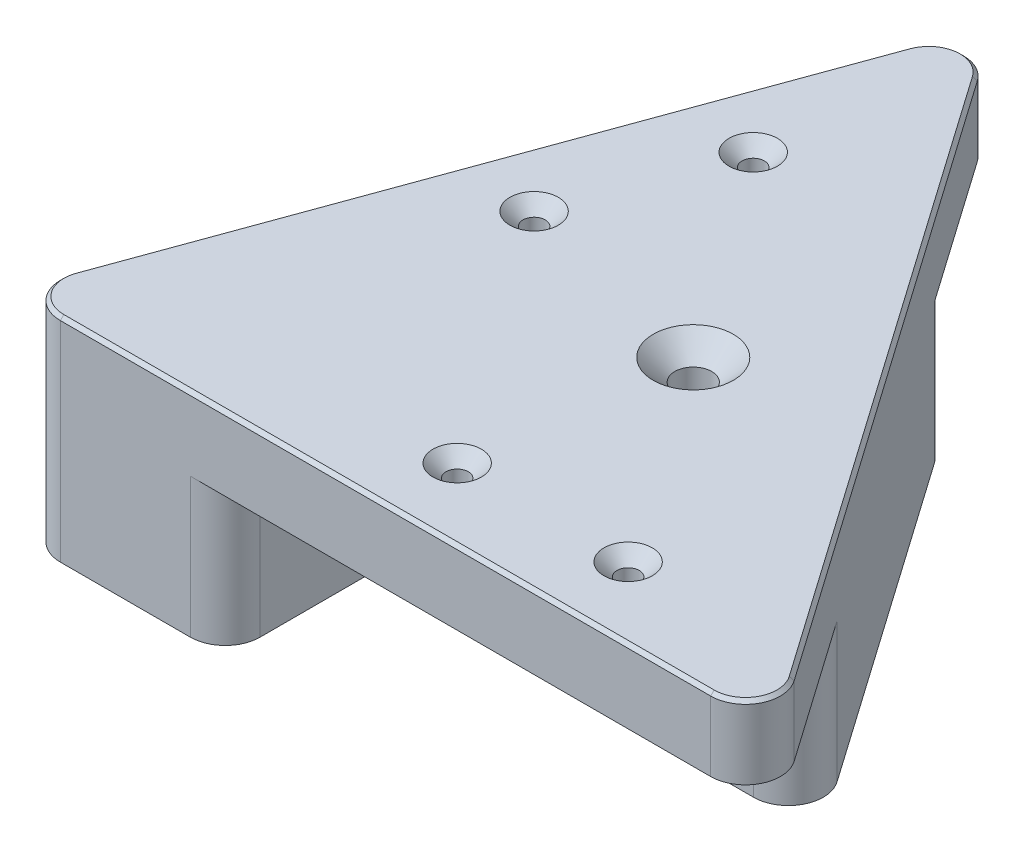
SolidWorks part; units mm, degrees
material "acero"
ref_plane "Alzado" through (0, 0, 0) normal (0, 0, 1) x (1, 0, 0)
ref_plane "Planta" through (0, 0, 0) normal (0, 1, 0) x (1, 0, 0)
ref_plane "Vista lateral" through (0, 0, 0) normal (1, 0, 0) x (0, 0, -1)
sketch "Sketch1" plane through (0, 0, 0) normal (0, 1, 0) x (1, 0, 0)
  line L0 (-55, 0) -> (55, 0)
  line L1 (-55, 0) -> (-17.3778, 103.3662)
  line L2 (-17.3778, 103.3662) -> (55, 0)
  line L3 (-24.223, 20.5) -> (40.6457, 20.5)
  line L4 (-25.2099, 21.9095) -> (-3.0235, 82.8662)
  line L5 (-25.723, 20.5) -> (1.8859, 96.3548) construction
  line L6 (-25.723, 20.5) -> (55, 20.5) construction
  line L7 (-25.723, 20.5) -> (-25.723, 0) construction
  line L8 (-7.6718, 30.0667) -> (12.8282, 30.0667)
  line L9 (-7.6718, 30.0667) -> (-7.6718, 50.5667)
  line L10 (-7.6718, 50.5667) -> (12.8282, 50.5667)
  line L11 (12.8282, 30.0667) -> (12.8282, 50.5667)
  line L12 (-7.6718, 30.0667) -> (12.8282, 50.5667) construction
  line L13 (-7.6718, 50.5667) -> (12.8282, 30.0667) construction
  line L14 (-25.723, 20.5) -> (-44.9867, 27.5114) construction
  line L15 (-10.2007, 93.1162) -> (-35.3548, 24.0057) construction
  line L16 (-25.723, 10.25) -> (47.8229, 10.25) construction
  line L17 (-24.223, 20.5) -> (-24.223, 0)
  line L18 (-3.5479, 53.4543) -> (-10.5593, 34.1906)
  line L19 (-3.5479, 53.4543) -> (15.7158, 46.4428)
  line L20 (15.7158, 46.4428) -> (8.7044, 27.1791)
  line L21 (-10.5593, 34.1906) -> (8.7044, 27.1791)
  line L22 (-3.5479, 53.4543) -> (8.7044, 27.1791) construction
  line L23 (15.7158, 46.4428) -> (-10.5593, 34.1906) construction
  line L24 (-25.2099, 21.9095) -> (-44.4736, 28.921)
  line L25 (-24.223, 21.5503) -> (-44.4736, 28.921) construction
  line L26 (-24.223, 21.5503) -> (-24.223, 0) construction
  circle A0 centre (2.5782, 40.3167) radius 19.8167 construction
  circle A1 centre (-1.2077, 10.25) radius 1
  circle A2 centre (23.3076, 10.25) radius 1
  circle A3 centre (-26.9701, 47.0425) radius 1
  circle A4 centre (-18.5854, 70.0794) radius 1
  circle A6 centre (2.5782, 40.3167) radius 1
  point P37 (15.8814, 48.8851)
  point P38 (7.6861, 50.3243)
  point P39 (7.9832, 50.4054)
  point P40 (8.0839, 49.7026)
  point P46 (0, 0)
  dimension "D9" = 2
  dimension "D1" = 110
  dimension "D2" = 110
  dimension "D5" = 20.5
  dimension "D6" = 20.5
  dimension "D7" = 10.25
  dimension "D8" = 10.25
  dimension "D11" = 73.5458
  dimension "D10" = 24.5153
  dimension "D12" = 24.5153
  dimension "D13" = 24.5153
  dimension "D14" = 24.5153
  dimension "D3" = 70
  dimension "D4" = 20.5
  dimension "D16" = 1.5
extrude "Main Body" add sketch "Sketch1" along normal blind 10.5 contours L7 L14 L1 L0 | L3 L7 L0 L2 A2 A1 | L14 L4 L2 L1 A4 A3 | L4 L3 L2 L11 L8 L9 L10 | L8 L11 L10 L9 | L18 L10 L9 | L19 L18 L10 | L10 L19 L11 | L20 L19 L11 | L11 L20 L8 | L8 L21 L20 | L21 L9 L8 | L18 L21 L9 region at (-8.0023, 0, -32.9082) region at (11.9228, 0, -9.9082) region at (-22.8004, 0, -59.4981) region at (-4.8576, 0, -31.091) region at (-3.3513, 0, -31.8756) region at (6.4102, 0, -29.1042) region at (-8.6343, 0, -36.4847) region at (11.8039, 0, -32.8809) region at (-6.6475, 0, -47.7525) region at (13.7907, 0, -44.1487) region at (-1.2538, 0, -51.5292) region at (10.014, 0, -49.5424)
extrude "Profile Stops" add sketch "Sketch1<3>" against normal blind 20 contours L7 L14 L1 L0 region at (-8.0023, 0, -32.9082)
sketch "Sketch1<3>" plane through (0, 0, 0) normal (0, 1, 0) x (1, 0, 0) same geometry as "Sketch1"
hole_wizard "CSK for M3 Hex Socket Countersunk Head Screw1" positions "3DSketch1" profile "Sketch4" countersink size "M3" standard "DIN" end condition up to next
sketch3d "3DSketch1"
  line L0 (-18.5854, 10.5, -70.0794) -> (-18.5854, 0, -70.0794) construction
  line L1 (-26.9701, 10.5, -47.0425) -> (-26.9701, 0, -47.0425) construction
  line L2 (23.3076, 10.5, -10.25) -> (23.3076, 0, -10.25) construction
  line L3 (-1.2077, 10.5, -10.25) -> (-1.2077, 0, -10.25) construction
  point P0 (-18.5854, 10.5, -70.0794)
  point P4 (-26.9701, 10.5, -47.0425)
  point P8 (23.3076, 10.5, -10.25)
  point P12 (-1.2077, 10.5, -10.25)
sketch "Sketch4" plane through (-18.5854, 10.5, -70.0794) normal (1, 0, 0) x (0, 0, 1)
  line L0 (0, 0) -> (0, 30.5)
  line L1 (0, 30.5) -> (1.6, 30.5)
  line L2 (1.6, 30.5) -> (1.6, 1.87)
  line L3 (1.6, 1.87) -> (3.47, 0)
  line L5 (3.47, 0) -> (0, 0)
  line L6 (-1.6, 1.87) -> (-3.47, 0) construction
  line L11 (0, -6.35) -> (0, 107.95) construction
  dimension "Thru Hole Dia." = 3.2
  dimension "Thru Hole Depth" = 30.5
  dimension "Near C'Sink Dia." = 6.94
  dimension "Near C'Sink Angle" = 90
hole_wizard "CSK for M5 Hex Socket Countersunk Head Screw1" positions "3DSketch2" profile "Sketch5" countersink size "M5" standard "DIN" end condition up to next
sketch3d "3DSketch2"
  line L0 (2.5782, 10.5, -40.3167) -> (2.5782, 0, -40.3167) construction
  point P0 (2.5782, 10.5, -40.3167)
sketch "Sketch5" plane through (2.5782, 10.5, -40.3167) normal (1, 0, 0) x (0, 0, 1)
  line L0 (0, 0) -> (0, 30.5)
  line L1 (0, 30.5) -> (2.65, 30.5)
  line L2 (2.65, 30.5) -> (2.65, 3.085)
  line L3 (2.65, 3.085) -> (5.735, 0)
  line L5 (5.735, 0) -> (0, 0)
  line L6 (-2.65, 3.085) -> (-5.735, 0) construction
  line L11 (0, -6.35) -> (0, 107.95) construction
  dimension "Thru Hole Dia." = 5.3
  dimension "Thru Hole Depth" = 30.5
  dimension "Near C'Sink Dia." = 11.47
  dimension "Near C'Sink Angle" = 90
fillet "Fillet1" radius 5 3 edges at (-55, -4.75, 0) (-24.223, -10, 0) (-44.4736, -10, -28.921)
fillet "Fillet3" radius 5 4 edges at (55, 5.25, 0) (40.6457, -10, -20.5) (-3.0235, -10, -82.8662) (-17.3778, 5.25, -103.3662)
draft "Draft1" type of draft neutral plane draft angle 0.5 faces to draft 16 face at (11.2918, -10, -30.0667) face at (9.2299, -10, -28.6229) face at (4.7376, -10, -28.6229) face at (-3.4505, -10, -30.0667) face at (-7.6718, -10, -31.6031) face at (-9.1156, -10, -33.6651) face at (-9.1156, -10, -38.1573) face at (-6.1353, -10, -50.5667) face at (-7.6718, -10, -46.3454) face at (-4.0734, -10, -52.0105) face at (0.4188, -10, -52.0105) face at (8.6069, -10, -50.5667) face at (12.8282, -10, -49.0303) face at (14.272, -10, -46.9683) face at (14.272, -10, -42.4761) face at (12.8282, -10, -34.288) neutral plane through (0, 0, 0) neutral plane normal (0, -1, 0) parameters "D1"=0.5
chamfer "Chamfer2" distance 0.5 angle 45 6 edges at (49.8301, 10.5, -2.6913) (-1.2321, 10.5, 0) (18.8111, 10.5, -51.6831) (-51.955, 10.5, -2.1321) (-16.617, 10.5, -97.5876) (-36.6103, 10.5, -50.5253)
equation "\"D2@Sketch1\"=\"D1@Sketch1\""
equation "\"D6@Sketch1\"=\"D5@Sketch1\""
equation "\"D7@Sketch1\"=\"D4@Sketch1\"/2"
equation "\"D8@Sketch1\"=\"D7@Sketch1\""
equation "\"D10@Sketch1\"=\"D11@Sketch1\"/3"
equation "\"D12@Sketch1\"=\"D10@Sketch1\""
equation "\"D13@Sketch1\"=\"D10@Sketch1\""
equation "\"D14@Sketch1\"=\"D13@Sketch1\""
